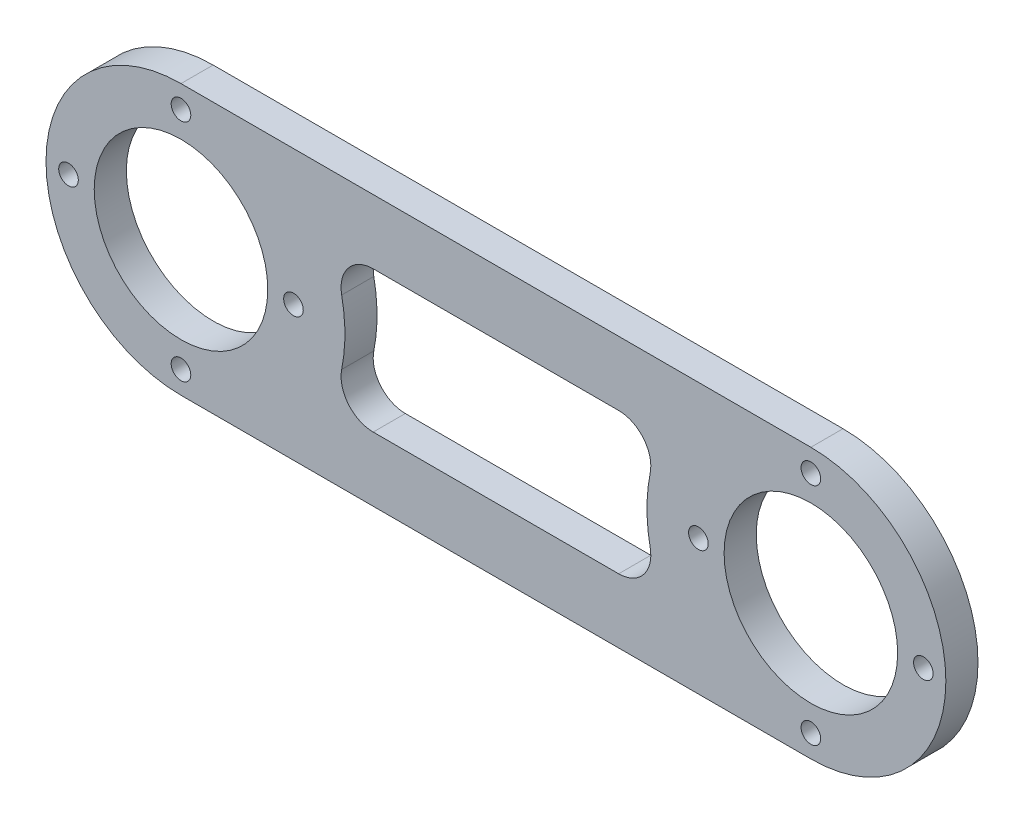
SolidWorks part; units mm, degrees
material "6061 Alloy"
ref_plane "Front Plane" through (0, 0, 0) normal (0, 0, 1) x (1, 0, 0)
ref_plane "Top Plane" through (0, 0, 0) normal (0, 1, 0) x (1, 0, 0)
ref_plane "Right Plane" through (0, 0, 0) normal (1, 0, 0) x (0, 0, -1)
sketch "Sketch1" plane through (0, 0, 0) normal (0, 0, 1) x (1, 0, 0)
  line L0 (49, 26) -> (-49, 26) construction
  line L1 (-49, -16) -> (49, -16) construction
  line L2 (49, 26) -> (-49, 26)
  line L3 (-49, -16) -> (49, -16)
  circle A0 centre (49, 5) radius 21 construction
  arc A1 (-49, 26) -> (-49, -16) centre (-49, 5) ccw
  circle A3 centre (-66.5, 5) radius 1.5 construction
  circle A4 centre (-49, 22.5) radius 1.5 construction
  circle A5 centre (-31.5, 5) radius 1.5 construction
  circle A6 centre (-49, -12.5) radius 1.5 construction
  circle A8 centre (31.5, 5) radius 1.5 construction
  circle A9 centre (49, 22.5) radius 1.5 construction
  circle A10 centre (66.5, 5) radius 1.5 construction
  circle A11 centre (49, -12.5) radius 1.5 construction
  arc A12 (49, -16) -> (49, 26) centre (49, 5) ccw
  circle A14 centre (-49, 5) radius 13
  circle A15 centre (-66.5, 5) radius 1.5
  circle A16 centre (-49, 22.5) radius 1.5
  circle A17 centre (-31.5, 5) radius 1.5
  circle A18 centre (-49, -12.5) radius 1.5
  circle A19 centre (49, 5) radius 13
  circle A20 centre (31.5, 5) radius 1.5
  circle A21 centre (49, 22.5) radius 1.5
  circle A22 centre (66.5, 5) radius 1.5
  circle A23 centre (49, -12.5) radius 1.5
  point P3 (0, 0)
  point P5 (0, 0)
  point P15 (-49.279, -16)
  point P24 (-53.0918, 5)
  point P25 (0, 0)
  dimension "D1" = 26
extrude "Boss-Extrude1" add sketch "Sketch1" along normal blind 5
sketch "Sketch2" plane through (0, 0, 0) normal (0, 0, -1) x (-1, 0, 0)
  circle A0 centre (-49, 5) radius 13.5
  circle A1 centre (49, 5) radius 13.5
  dimension "D1" = 27
extrude "Cut-Extrude1" cut sketch "Sketch2" against normal blind 10
sketch "Sketch3" plane through (0, 0, 5) normal (0, 0, 1) x (1, 0, 0)
  line L0 (-49, -16) -> (49, -16) construction
  line L1 (-25.9946, 16) -> (25.9946, 16)
  line L3 (-25.9946, -6) -> (25.9946, -6)
  line L5 (49, 26) -> (-49, 26) construction
  arc A0 (-25.9946, 16) -> (-25.9946, -6) centre (-49, 5) cw
  arc A1 (25.9946, 16) -> (25.9946, -6) centre (49, 5) ccw
  circle A2 centre (-49, 5) radius 13.5 construction
  circle A3 centre (49, 5) radius 13.5 construction
  dimension "D3" = 12
  dimension "D4" = 12
  dimension "D1" = 10
  dimension "D2" = 10
extrude "Cut-Extrude2" cut sketch "Sketch3" against normal blind 10
fillet "Fillet1" radius 5 4 edges at (25.9946, -6, 2.5) (-25.9946, -6, 2.5) (25.9946, 16, 2.5) (-25.9946, 16, 2.5)
sketch "Sketch4" plane through (0, 0, 5) normal (0, 0, 1) x (1, 0, 0)
  circle A0 centre (-49, 22.5) radius 1.525
  circle A1 centre (-66.5, 5) radius 1.525
  circle A2 centre (-31.5, 5) radius 1.525
  circle A3 centre (-49, -12.5) radius 1.525
  circle A4 centre (49, 22.5) radius 1.525
  circle A5 centre (31.5, 5) radius 1.525
  circle A6 centre (66.5, 5) radius 1.525
  circle A7 centre (49, -12.5) radius 1.525
  dimension "D1" = 3.05
extrude "Cut-Extrude3" cut sketch "Sketch4" against normal blind 10
